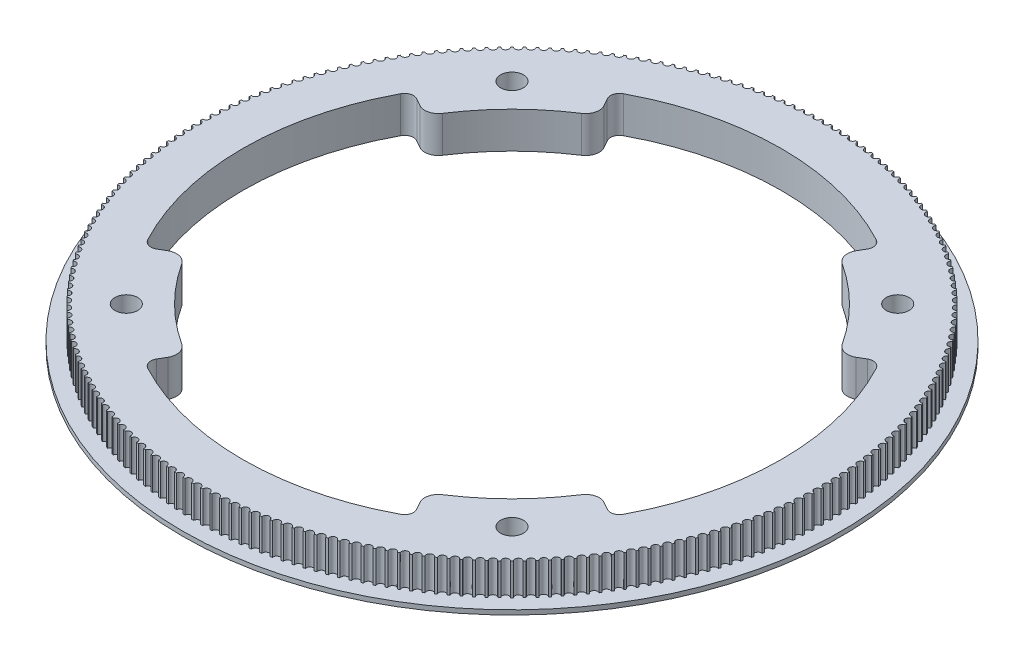
SolidWorks part; units mm, degrees
material "ABS"
ref_plane "Front Plane" through (0, 0, 0) normal (0, 0, 1) x (1, 0, 0)
ref_plane "Top Plane" through (0, 0, 0) normal (0, 1, 0) x (1, 0, 0)
ref_plane "Right Plane" through (0, 0, 0) normal (1, 0, 0) x (0, 0, -1)
sketch "Sketch1" plane through (0, 0, 0) normal (0, 1, 0) x (1, 0, 0)
  arc A0 (-0.76, 69.2508) -> (-1.2179, 69.2443) centre (0, 0) ccw
  arc A1 (-0.76, 69.2508) -> (0.76, 69.2508) centre (0, 69.255) ccw
  arc A2 (1.2179, 69.2443) -> (2.7372, 69.2009) centre (1.9776, 69.2268) ccw
  arc A3 (3.1947, 69.1813) -> (4.7122, 69.0945) centre (3.9537, 69.1421) ccw
  arc A4 (5.1689, 69.0618) -> (6.6833, 68.9318) centre (5.9265, 69.001) ccw
  arc A5 (7.139, 68.8861) -> (8.649, 68.7128) centre (7.8945, 68.8036) ccw
  arc A6 (9.1032, 68.6541) -> (10.6077, 68.4378) centre (9.856, 68.5501) ccw
  arc A7 (11.0599, 68.3662) -> (12.5577, 68.107) centre (11.8095, 68.2407) ccw
  arc A8 (13.0077, 68.0225) -> (14.4974, 67.7206) centre (13.7534, 67.8756) ccw
  arc A9 (14.9449, 67.6233) -> (16.4253, 67.279) centre (15.686, 67.4552) ccw
  arc A10 (16.8698, 67.1689) -> (18.3399, 66.7825) centre (17.6059, 66.9798) ccw
  arc A11 (18.781, 66.6598) -> (20.2394, 66.2316) centre (19.5114, 66.4497) ccw
  arc A12 (20.6769, 66.0963) -> (22.1225, 65.6266) centre (21.401, 65.8654) ccw
  arc A13 (22.5559, 65.4789) -> (23.9875, 64.9681) centre (23.2731, 65.2274) ccw
  arc A14 (24.4165, 64.8081) -> (25.8329, 64.2566) centre (25.1262, 64.5362) ccw
  arc A15 (26.2572, 64.0844) -> (27.6573, 63.4927) centre (26.9589, 63.7924) ccw
  arc A16 (28.0765, 63.3085) -> (29.4591, 62.6771) centre (28.7696, 62.9966) ccw
  arc A17 (29.8729, 62.4809) -> (31.2369, 61.8103) centre (30.5568, 62.1493) ccw
  arc A18 (31.6449, 61.6024) -> (32.9893, 60.8931) centre (32.319, 61.2514) ccw
  arc A19 (33.3912, 60.6736) -> (34.7147, 59.9262) centre (34.055, 60.3035) ccw
  arc A20 (35.1101, 59.6953) -> (36.4118, 58.9104) centre (35.7631, 59.3065) ccw
  arc A21 (36.8005, 58.6684) -> (38.0792, 57.8466) centre (37.4421, 58.261) ccw
  arc A22 (38.4608, 57.5936) -> (39.7155, 56.7356) centre (39.0905, 57.1681) ccw
  arc A23 (40.0898, 56.4718) -> (41.3195, 55.5784) centre (40.7071, 56.0285) ccw
  arc A24 (41.686, 55.304) -> (42.8897, 54.3758) centre (42.2904, 54.8432) ccw
  arc A25 (43.2483, 54.091) -> (44.425, 53.1289) centre (43.8393, 53.6132) ccw
  arc A26 (44.7753, 52.834) -> (45.924, 51.8386) centre (45.3524, 52.3394) ccw
  arc A27 (46.2658, 51.5338) -> (47.3856, 50.5061) centre (46.8285, 51.023) ccw
  arc A28 (47.7185, 50.1916) -> (48.8085, 49.1323) centre (48.2664, 49.665) ccw
  arc A29 (49.1323, 48.8085) -> (50.1916, 47.7185) centre (49.665, 48.2664) ccw
  arc A30 (50.5061, 47.3856) -> (51.5338, 46.2658) centre (51.023, 46.8285) ccw
  arc A31 (51.8386, 45.924) -> (52.834, 44.7753) centre (52.3394, 45.3524) ccw
  arc A32 (53.1289, 44.425) -> (54.091, 43.2483) centre (53.6132, 43.8393) ccw
  arc A33 (54.3758, 42.8897) -> (55.304, 41.686) centre (54.8432, 42.2904) ccw
  arc A34 (55.5784, 41.3195) -> (56.4718, 40.0898) centre (56.0285, 40.7071) ccw
  arc A35 (56.7356, 39.7155) -> (57.5936, 38.4608) centre (57.1681, 39.0905) ccw
  arc A36 (57.8466, 38.0792) -> (58.6684, 36.8005) centre (58.261, 37.4421) ccw
  arc A37 (58.9104, 36.4118) -> (59.6953, 35.1101) centre (59.3065, 35.7631) ccw
  arc A38 (59.9262, 34.7147) -> (60.6736, 33.3912) centre (60.3035, 34.055) ccw
  arc A39 (60.8931, 32.9893) -> (61.6024, 31.6449) centre (61.2514, 32.319) ccw
  arc A40 (61.8103, 31.2369) -> (62.4809, 29.8729) centre (62.1493, 30.5568) ccw
  arc A41 (62.6771, 29.4591) -> (63.3085, 28.0765) centre (62.9966, 28.7696) ccw
  arc A42 (63.4927, 27.6573) -> (64.0844, 26.2572) centre (63.7924, 26.9589) ccw
  arc A43 (64.2566, 25.8329) -> (64.8081, 24.4165) centre (64.5362, 25.1262) ccw
  arc A44 (64.9681, 23.9875) -> (65.4789, 22.5559) centre (65.2274, 23.2731) ccw
  arc A45 (65.6266, 22.1225) -> (66.0963, 20.6769) centre (65.8654, 21.401) ccw
  arc A46 (66.2316, 20.2394) -> (66.6598, 18.781) centre (66.4497, 19.5114) ccw
  arc A47 (66.7825, 18.3399) -> (67.1689, 16.8698) centre (66.9798, 17.6059) ccw
  arc A48 (67.279, 16.4253) -> (67.6233, 14.9449) centre (67.4552, 15.686) ccw
  arc A49 (67.7206, 14.4974) -> (68.0225, 13.0077) centre (67.8756, 13.7534) ccw
  arc A50 (68.107, 12.5577) -> (68.3662, 11.0599) centre (68.2407, 11.8095) ccw
  arc A51 (68.4378, 10.6077) -> (68.6541, 9.1032) centre (68.5501, 9.856) ccw
  arc A52 (68.7128, 8.649) -> (68.8861, 7.139) centre (68.8036, 7.8945) ccw
  arc A53 (68.9318, 6.6833) -> (69.0618, 5.1689) centre (69.001, 5.9265) ccw
  arc A54 (69.0945, 4.7122) -> (69.1813, 3.1947) centre (69.1421, 3.9537) ccw
  arc A55 (69.2009, 2.7372) -> (69.2443, 1.2179) centre (69.2268, 1.9776) ccw
  arc A56 (69.2508, 0.76) -> (69.2508, -0.76) centre (69.255, 0) ccw
  arc A57 (69.2443, -1.2179) -> (69.2009, -2.7372) centre (69.2268, -1.9776) ccw
  arc A58 (69.1813, -3.1947) -> (69.0945, -4.7122) centre (69.1421, -3.9537) ccw
  arc A59 (69.0618, -5.1689) -> (68.9318, -6.6833) centre (69.001, -5.9265) ccw
  arc A60 (68.8861, -7.139) -> (68.7128, -8.649) centre (68.8036, -7.8945) ccw
  arc A61 (68.6541, -9.1032) -> (68.4378, -10.6077) centre (68.5501, -9.856) ccw
  arc A62 (68.3662, -11.0599) -> (68.107, -12.5577) centre (68.2407, -11.8095) ccw
  arc A63 (68.0225, -13.0077) -> (67.7206, -14.4974) centre (67.8756, -13.7534) ccw
  arc A64 (67.6233, -14.9449) -> (67.279, -16.4253) centre (67.4552, -15.686) ccw
  arc A65 (67.1689, -16.8698) -> (66.7825, -18.3399) centre (66.9798, -17.6059) ccw
  arc A66 (66.6598, -18.781) -> (66.2316, -20.2394) centre (66.4497, -19.5114) ccw
  arc A67 (66.0963, -20.6769) -> (65.6266, -22.1225) centre (65.8654, -21.401) ccw
  arc A68 (65.4789, -22.5559) -> (64.9681, -23.9875) centre (65.2274, -23.2731) ccw
  arc A69 (64.8081, -24.4165) -> (64.2566, -25.8329) centre (64.5362, -25.1262) ccw
  arc A70 (64.0844, -26.2572) -> (63.4927, -27.6573) centre (63.7924, -26.9589) ccw
  arc A71 (63.3085, -28.0765) -> (62.6771, -29.4591) centre (62.9966, -28.7696) ccw
  arc A72 (62.4809, -29.8729) -> (61.8103, -31.2369) centre (62.1493, -30.5568) ccw
  arc A73 (61.6024, -31.6449) -> (60.8931, -32.9893) centre (61.2514, -32.319) ccw
  arc A74 (60.6736, -33.3912) -> (59.9262, -34.7147) centre (60.3035, -34.055) ccw
  arc A75 (59.6953, -35.1101) -> (58.9104, -36.4118) centre (59.3065, -35.7631) ccw
  arc A76 (58.6684, -36.8005) -> (57.8466, -38.0792) centre (58.261, -37.4421) ccw
  arc A77 (57.5936, -38.4608) -> (56.7356, -39.7155) centre (57.1681, -39.0905) ccw
  arc A78 (56.4718, -40.0898) -> (55.5784, -41.3195) centre (56.0285, -40.7071) ccw
  arc A79 (55.304, -41.686) -> (54.3758, -42.8897) centre (54.8432, -42.2904) ccw
  arc A80 (54.091, -43.2483) -> (53.1289, -44.425) centre (53.6132, -43.8393) ccw
  arc A81 (52.834, -44.7753) -> (51.8386, -45.924) centre (52.3394, -45.3524) ccw
  arc A82 (51.5338, -46.2658) -> (50.5061, -47.3856) centre (51.023, -46.8285) ccw
  arc A83 (50.1916, -47.7185) -> (49.1323, -48.8085) centre (49.665, -48.2664) ccw
  arc A84 (48.8085, -49.1323) -> (47.7185, -50.1916) centre (48.2664, -49.665) ccw
  arc A85 (47.3856, -50.5061) -> (46.2658, -51.5338) centre (46.8285, -51.023) ccw
  arc A86 (45.924, -51.8386) -> (44.7753, -52.834) centre (45.3524, -52.3394) ccw
  arc A87 (44.425, -53.1289) -> (43.2483, -54.091) centre (43.8393, -53.6132) ccw
  arc A88 (42.8897, -54.3758) -> (41.686, -55.304) centre (42.2904, -54.8432) ccw
  arc A89 (41.3195, -55.5784) -> (40.0898, -56.4718) centre (40.7071, -56.0285) ccw
  arc A90 (39.7155, -56.7356) -> (38.4608, -57.5936) centre (39.0905, -57.1681) ccw
  arc A91 (38.0792, -57.8466) -> (36.8005, -58.6684) centre (37.4421, -58.261) ccw
  arc A92 (36.4118, -58.9104) -> (35.1101, -59.6953) centre (35.7631, -59.3065) ccw
  arc A93 (34.7147, -59.9262) -> (33.3912, -60.6736) centre (34.055, -60.3035) ccw
  arc A94 (32.9893, -60.8931) -> (31.6449, -61.6024) centre (32.319, -61.2514) ccw
  arc A95 (31.2369, -61.8103) -> (29.8729, -62.4809) centre (30.5568, -62.1493) ccw
  arc A96 (29.4591, -62.6771) -> (28.0765, -63.3085) centre (28.7696, -62.9966) ccw
  arc A97 (27.6573, -63.4927) -> (26.2572, -64.0844) centre (26.9589, -63.7924) ccw
  arc A98 (25.8329, -64.2566) -> (24.4165, -64.8081) centre (25.1262, -64.5362) ccw
  arc A99 (23.9875, -64.9681) -> (22.5559, -65.4789) centre (23.2731, -65.2274) ccw
  arc A100 (22.1225, -65.6266) -> (20.6769, -66.0963) centre (21.401, -65.8654) ccw
  arc A101 (20.2394, -66.2316) -> (18.781, -66.6598) centre (19.5114, -66.4497) ccw
  arc A102 (18.3399, -66.7825) -> (16.8698, -67.1689) centre (17.6059, -66.9798) ccw
  arc A103 (16.4253, -67.279) -> (14.9449, -67.6233) centre (15.686, -67.4552) ccw
  arc A104 (14.4974, -67.7206) -> (13.0077, -68.0225) centre (13.7534, -67.8756) ccw
  arc A105 (12.5577, -68.107) -> (11.0599, -68.3662) centre (11.8095, -68.2407) ccw
  arc A106 (10.6077, -68.4378) -> (9.1032, -68.6541) centre (9.856, -68.5501) ccw
  arc A107 (8.649, -68.7128) -> (7.139, -68.8861) centre (7.8945, -68.8036) ccw
  arc A108 (6.6833, -68.9318) -> (5.1689, -69.0618) centre (5.9265, -69.001) ccw
  arc A109 (4.7122, -69.0945) -> (3.1947, -69.1813) centre (3.9537, -69.1421) ccw
  arc A110 (2.7372, -69.2009) -> (1.2179, -69.2443) centre (1.9776, -69.2268) ccw
  arc A111 (0.76, -69.2508) -> (-0.76, -69.2508) centre (0, -69.255) ccw
  arc A112 (-1.2179, -69.2443) -> (-2.7372, -69.2009) centre (-1.9776, -69.2268) ccw
  arc A113 (-3.1947, -69.1813) -> (-4.7122, -69.0945) centre (-3.9537, -69.1421) ccw
  arc A114 (-5.1689, -69.0618) -> (-6.6833, -68.9318) centre (-5.9265, -69.001) ccw
  arc A115 (-7.139, -68.8861) -> (-8.649, -68.7128) centre (-7.8945, -68.8036) ccw
  arc A116 (-9.1032, -68.6541) -> (-10.6077, -68.4378) centre (-9.856, -68.5501) ccw
  arc A117 (-11.0599, -68.3662) -> (-12.5577, -68.107) centre (-11.8095, -68.2407) ccw
  arc A118 (-13.0077, -68.0225) -> (-14.4974, -67.7206) centre (-13.7534, -67.8756) ccw
  arc A119 (-14.9449, -67.6233) -> (-16.4253, -67.279) centre (-15.686, -67.4552) ccw
  arc A120 (-16.8698, -67.1689) -> (-18.3399, -66.7825) centre (-17.6059, -66.9798) ccw
  arc A121 (-18.781, -66.6598) -> (-20.2394, -66.2316) centre (-19.5114, -66.4497) ccw
  arc A122 (-20.6769, -66.0963) -> (-22.1225, -65.6266) centre (-21.401, -65.8654) ccw
  arc A123 (-22.5559, -65.4789) -> (-23.9875, -64.9681) centre (-23.2731, -65.2274) ccw
  arc A124 (-24.4165, -64.8081) -> (-25.8329, -64.2566) centre (-25.1262, -64.5362) ccw
  arc A125 (-26.2572, -64.0844) -> (-27.6573, -63.4927) centre (-26.9589, -63.7924) ccw
  arc A126 (-28.0765, -63.3085) -> (-29.4591, -62.6771) centre (-28.7696, -62.9966) ccw
  arc A127 (-29.8729, -62.4809) -> (-31.2369, -61.8103) centre (-30.5568, -62.1493) ccw
  arc A128 (-31.6449, -61.6024) -> (-32.9893, -60.8931) centre (-32.319, -61.2514) ccw
  arc A129 (-33.3912, -60.6736) -> (-34.7147, -59.9262) centre (-34.055, -60.3035) ccw
  arc A130 (-35.1101, -59.6953) -> (-36.4118, -58.9104) centre (-35.7631, -59.3065) ccw
  arc A131 (-36.8005, -58.6684) -> (-38.0792, -57.8466) centre (-37.4421, -58.261) ccw
  arc A132 (-38.4608, -57.5936) -> (-39.7155, -56.7356) centre (-39.0905, -57.1681) ccw
  arc A133 (-40.0898, -56.4718) -> (-41.3195, -55.5784) centre (-40.7071, -56.0285) ccw
  arc A134 (-41.686, -55.304) -> (-42.8897, -54.3758) centre (-42.2904, -54.8432) ccw
  arc A135 (-43.2483, -54.091) -> (-44.425, -53.1289) centre (-43.8393, -53.6132) ccw
  arc A136 (-44.7753, -52.834) -> (-45.924, -51.8386) centre (-45.3524, -52.3394) ccw
  arc A137 (-46.2658, -51.5338) -> (-47.3856, -50.5061) centre (-46.8285, -51.023) ccw
  arc A138 (-47.7185, -50.1916) -> (-48.8085, -49.1323) centre (-48.2664, -49.665) ccw
  arc A139 (-49.1323, -48.8085) -> (-50.1916, -47.7185) centre (-49.665, -48.2664) ccw
  arc A140 (-50.5061, -47.3856) -> (-51.5338, -46.2658) centre (-51.023, -46.8285) ccw
  arc A141 (-51.8386, -45.924) -> (-52.834, -44.7753) centre (-52.3394, -45.3524) ccw
  arc A142 (-53.1289, -44.425) -> (-54.091, -43.2483) centre (-53.6132, -43.8393) ccw
  arc A143 (-54.3758, -42.8897) -> (-55.304, -41.686) centre (-54.8432, -42.2904) ccw
  arc A144 (-55.5784, -41.3195) -> (-56.4718, -40.0898) centre (-56.0285, -40.7071) ccw
  arc A145 (-56.7356, -39.7155) -> (-57.5936, -38.4608) centre (-57.1681, -39.0905) ccw
  arc A146 (-57.8466, -38.0792) -> (-58.6684, -36.8005) centre (-58.261, -37.4421) ccw
  arc A147 (-58.9104, -36.4118) -> (-59.6953, -35.1101) centre (-59.3065, -35.7631) ccw
  arc A148 (-59.9262, -34.7147) -> (-60.6736, -33.3912) centre (-60.3035, -34.055) ccw
  arc A149 (-60.8931, -32.9893) -> (-61.6024, -31.6449) centre (-61.2514, -32.319) ccw
  arc A150 (-61.8103, -31.2369) -> (-62.4809, -29.8729) centre (-62.1493, -30.5568) ccw
  arc A151 (-62.6771, -29.4591) -> (-63.3085, -28.0765) centre (-62.9966, -28.7696) ccw
  arc A152 (-63.4927, -27.6573) -> (-64.0844, -26.2572) centre (-63.7924, -26.9589) ccw
  arc A153 (-64.2566, -25.8329) -> (-64.8081, -24.4165) centre (-64.5362, -25.1262) ccw
  arc A154 (-64.9681, -23.9875) -> (-65.4789, -22.5559) centre (-65.2274, -23.2731) ccw
  arc A155 (-65.6266, -22.1225) -> (-66.0963, -20.6769) centre (-65.8654, -21.401) ccw
  arc A156 (-66.2316, -20.2394) -> (-66.6598, -18.781) centre (-66.4497, -19.5114) ccw
  arc A157 (-66.7825, -18.3399) -> (-67.1689, -16.8698) centre (-66.9798, -17.6059) ccw
  arc A158 (-67.279, -16.4253) -> (-67.6233, -14.9449) centre (-67.4552, -15.686) ccw
  arc A159 (-67.7206, -14.4974) -> (-68.0225, -13.0077) centre (-67.8756, -13.7534) ccw
  arc A160 (-68.107, -12.5577) -> (-68.3662, -11.0599) centre (-68.2407, -11.8095) ccw
  arc A161 (-68.4378, -10.6077) -> (-68.6541, -9.1032) centre (-68.5501, -9.856) ccw
  arc A162 (-68.7128, -8.649) -> (-68.8861, -7.139) centre (-68.8036, -7.8945) ccw
  arc A163 (-68.9318, -6.6833) -> (-69.0618, -5.1689) centre (-69.001, -5.9265) ccw
  arc A164 (-69.0945, -4.7122) -> (-69.1813, -3.1947) centre (-69.1421, -3.9537) ccw
  arc A165 (-69.2009, -2.7372) -> (-69.2443, -1.2179) centre (-69.2268, -1.9776) ccw
  arc A166 (-69.2508, -0.76) -> (-69.2508, 0.76) centre (-69.255, 0) ccw
  arc A167 (-69.2443, 1.2179) -> (-69.2009, 2.7372) centre (-69.2268, 1.9776) ccw
  arc A168 (-69.1813, 3.1947) -> (-69.0945, 4.7122) centre (-69.1421, 3.9537) ccw
  arc A169 (-69.0618, 5.1689) -> (-68.9318, 6.6833) centre (-69.001, 5.9265) ccw
  arc A170 (-68.8861, 7.139) -> (-68.7128, 8.649) centre (-68.8036, 7.8945) ccw
  arc A171 (-68.6541, 9.1032) -> (-68.4378, 10.6077) centre (-68.5501, 9.856) ccw
  arc A172 (-68.3662, 11.0599) -> (-68.107, 12.5577) centre (-68.2407, 11.8095) ccw
  arc A173 (-68.0225, 13.0077) -> (-67.7206, 14.4974) centre (-67.8756, 13.7534) ccw
  arc A174 (-67.6233, 14.9449) -> (-67.279, 16.4253) centre (-67.4552, 15.686) ccw
  arc A175 (-67.1689, 16.8698) -> (-66.7825, 18.3399) centre (-66.9798, 17.6059) ccw
  arc A176 (-66.6598, 18.781) -> (-66.2316, 20.2394) centre (-66.4497, 19.5114) ccw
  arc A177 (-66.0963, 20.6769) -> (-65.6266, 22.1225) centre (-65.8654, 21.401) ccw
  arc A178 (-65.4789, 22.5559) -> (-64.9681, 23.9875) centre (-65.2274, 23.2731) ccw
  arc A179 (-64.8081, 24.4165) -> (-64.2566, 25.8329) centre (-64.5362, 25.1262) ccw
  arc A180 (-64.0844, 26.2572) -> (-63.4927, 27.6573) centre (-63.7924, 26.9589) ccw
  arc A181 (-63.3085, 28.0765) -> (-62.6771, 29.4591) centre (-62.9966, 28.7696) ccw
  arc A182 (-62.4809, 29.8729) -> (-61.8103, 31.2369) centre (-62.1493, 30.5568) ccw
  arc A183 (-61.6024, 31.6449) -> (-60.8931, 32.9893) centre (-61.2514, 32.319) ccw
  arc A184 (-60.6736, 33.3912) -> (-59.9262, 34.7147) centre (-60.3035, 34.055) ccw
  arc A185 (-59.6953, 35.1101) -> (-58.9104, 36.4118) centre (-59.3065, 35.7631) ccw
  arc A186 (-58.6684, 36.8005) -> (-57.8466, 38.0792) centre (-58.261, 37.4421) ccw
  arc A187 (-57.5936, 38.4608) -> (-56.7356, 39.7155) centre (-57.1681, 39.0905) ccw
  arc A188 (-56.4718, 40.0898) -> (-55.5784, 41.3195) centre (-56.0285, 40.7071) ccw
  arc A189 (-55.304, 41.686) -> (-54.3758, 42.8897) centre (-54.8432, 42.2904) ccw
  arc A190 (-54.091, 43.2483) -> (-53.1289, 44.425) centre (-53.6132, 43.8393) ccw
  arc A191 (-52.834, 44.7753) -> (-51.8386, 45.924) centre (-52.3394, 45.3524) ccw
  arc A192 (-51.5338, 46.2658) -> (-50.5061, 47.3856) centre (-51.023, 46.8285) ccw
  arc A193 (-50.1916, 47.7185) -> (-49.1323, 48.8085) centre (-49.665, 48.2664) ccw
  arc A194 (-48.8085, 49.1323) -> (-47.7185, 50.1916) centre (-48.2664, 49.665) ccw
  arc A195 (-47.3856, 50.5061) -> (-46.2658, 51.5338) centre (-46.8285, 51.023) ccw
  arc A196 (-45.924, 51.8386) -> (-44.7753, 52.834) centre (-45.3524, 52.3394) ccw
  arc A197 (-44.425, 53.1289) -> (-43.2483, 54.091) centre (-43.8393, 53.6132) ccw
  arc A198 (-42.8897, 54.3758) -> (-41.686, 55.304) centre (-42.2904, 54.8432) ccw
  arc A199 (-41.3195, 55.5784) -> (-40.0898, 56.4718) centre (-40.7071, 56.0285) ccw
  arc A200 (-39.7155, 56.7356) -> (-38.4608, 57.5936) centre (-39.0905, 57.1681) ccw
  arc A201 (-38.0792, 57.8466) -> (-36.8005, 58.6684) centre (-37.4421, 58.261) ccw
  arc A202 (-36.4118, 58.9104) -> (-35.1101, 59.6953) centre (-35.7631, 59.3065) ccw
  arc A203 (-34.7147, 59.9262) -> (-33.3912, 60.6736) centre (-34.055, 60.3035) ccw
  arc A204 (-32.9893, 60.8931) -> (-31.6449, 61.6024) centre (-32.319, 61.2514) ccw
  arc A205 (-31.2369, 61.8103) -> (-29.8729, 62.4809) centre (-30.5568, 62.1493) ccw
  arc A206 (-29.4591, 62.6771) -> (-28.0765, 63.3085) centre (-28.7696, 62.9966) ccw
  arc A207 (-27.6573, 63.4927) -> (-26.2572, 64.0844) centre (-26.9589, 63.7924) ccw
  arc A208 (-25.8329, 64.2566) -> (-24.4165, 64.8081) centre (-25.1262, 64.5362) ccw
  arc A209 (-23.9875, 64.9681) -> (-22.5559, 65.4789) centre (-23.2731, 65.2274) ccw
  arc A210 (-22.1225, 65.6266) -> (-20.6769, 66.0963) centre (-21.401, 65.8654) ccw
  arc A211 (-20.2394, 66.2316) -> (-18.781, 66.6598) centre (-19.5114, 66.4497) ccw
  arc A212 (-18.3399, 66.7825) -> (-16.8698, 67.1689) centre (-17.6059, 66.9798) ccw
  arc A213 (-16.4253, 67.279) -> (-14.9449, 67.6233) centre (-15.686, 67.4552) ccw
  arc A214 (-14.4974, 67.7206) -> (-13.0077, 68.0225) centre (-13.7534, 67.8756) ccw
  arc A215 (-12.5577, 68.107) -> (-11.0599, 68.3662) centre (-11.8095, 68.2407) ccw
  arc A216 (-10.6077, 68.4378) -> (-9.1032, 68.6541) centre (-9.856, 68.5501) ccw
  arc A217 (-8.649, 68.7128) -> (-7.139, 68.8861) centre (-7.8945, 68.8036) ccw
  arc A218 (-6.6833, 68.9318) -> (-5.1689, 69.0618) centre (-5.9265, 69.001) ccw
  arc A219 (-4.7122, 69.0945) -> (-3.1947, 69.1813) centre (-3.9537, 69.1421) ccw
  arc A220 (-2.7372, 69.2009) -> (-1.2179, 69.2443) centre (-1.9776, 69.2268) ccw
  arc A221 (1.2179, 69.2443) -> (0.76, 69.2508) centre (0, 0) ccw
  arc A222 (3.1947, 69.1813) -> (2.7372, 69.2009) centre (0, 0) ccw
  arc A223 (5.1689, 69.0618) -> (4.7122, 69.0945) centre (0, 0) ccw
  arc A224 (7.139, 68.8861) -> (6.6833, 68.9318) centre (0, 0) ccw
  arc A225 (9.1032, 68.6541) -> (8.649, 68.7128) centre (0, 0) ccw
  arc A226 (11.0599, 68.3662) -> (10.6077, 68.4378) centre (0, 0) ccw
  arc A227 (13.0077, 68.0225) -> (12.5577, 68.107) centre (0, 0) ccw
  arc A228 (14.9449, 67.6233) -> (14.4974, 67.7206) centre (0, 0) ccw
  arc A229 (16.8698, 67.1689) -> (16.4253, 67.279) centre (0, 0) ccw
  arc A230 (18.781, 66.6598) -> (18.3399, 66.7825) centre (0, 0) ccw
  arc A231 (20.6769, 66.0963) -> (20.2394, 66.2316) centre (0, 0) ccw
  arc A232 (22.5559, 65.4789) -> (22.1225, 65.6266) centre (0, 0) ccw
  arc A233 (24.4165, 64.8081) -> (23.9875, 64.9681) centre (0, 0) ccw
  arc A234 (26.2572, 64.0844) -> (25.8329, 64.2566) centre (0, 0) ccw
  arc A235 (28.0765, 63.3085) -> (27.6573, 63.4927) centre (0, 0) ccw
  arc A236 (29.8729, 62.4809) -> (29.4591, 62.6771) centre (0, 0) ccw
  arc A237 (31.6449, 61.6024) -> (31.2369, 61.8103) centre (0, 0) ccw
  arc A238 (33.3912, 60.6736) -> (32.9893, 60.8931) centre (0, 0) ccw
  arc A239 (35.1101, 59.6953) -> (34.7147, 59.9262) centre (0, 0) ccw
  arc A240 (36.8005, 58.6684) -> (36.4118, 58.9104) centre (0, 0) ccw
  arc A241 (38.4608, 57.5936) -> (38.0792, 57.8466) centre (0, 0) ccw
  arc A242 (40.0898, 56.4718) -> (39.7155, 56.7356) centre (0, 0) ccw
  arc A243 (41.686, 55.304) -> (41.3195, 55.5784) centre (0, 0) ccw
  arc A244 (43.2483, 54.091) -> (42.8897, 54.3758) centre (0, 0) ccw
  arc A245 (44.7753, 52.834) -> (44.425, 53.1289) centre (0, 0) ccw
  arc A246 (46.2658, 51.5338) -> (45.924, 51.8386) centre (0, 0) ccw
  arc A247 (47.7185, 50.1916) -> (47.3856, 50.5061) centre (0, 0) ccw
  arc A248 (49.1323, 48.8085) -> (48.8085, 49.1323) centre (0, 0) ccw
  arc A249 (50.5061, 47.3856) -> (50.1916, 47.7185) centre (0, 0) ccw
  arc A250 (51.8386, 45.924) -> (51.5338, 46.2658) centre (0, 0) ccw
  arc A251 (53.1289, 44.425) -> (52.834, 44.7753) centre (0, 0) ccw
  arc A252 (54.3758, 42.8897) -> (54.091, 43.2483) centre (0, 0) ccw
  arc A253 (55.5784, 41.3195) -> (55.304, 41.686) centre (0, 0) ccw
  arc A254 (56.7356, 39.7155) -> (56.4718, 40.0898) centre (0, 0) ccw
  arc A255 (57.8466, 38.0792) -> (57.5936, 38.4608) centre (0, 0) ccw
  arc A256 (58.9104, 36.4118) -> (58.6684, 36.8005) centre (0, 0) ccw
  arc A257 (59.9262, 34.7147) -> (59.6953, 35.1101) centre (0, 0) ccw
  arc A258 (60.8931, 32.9893) -> (60.6736, 33.3912) centre (0, 0) ccw
  arc A259 (61.8103, 31.2369) -> (61.6024, 31.6449) centre (0, 0) ccw
  arc A260 (62.6771, 29.4591) -> (62.4809, 29.8729) centre (0, 0) ccw
  arc A261 (63.4927, 27.6573) -> (63.3085, 28.0765) centre (0, 0) ccw
  arc A262 (64.2566, 25.8329) -> (64.0844, 26.2572) centre (0, 0) ccw
  arc A263 (64.9681, 23.9875) -> (64.8081, 24.4165) centre (0, 0) ccw
  arc A264 (65.6266, 22.1225) -> (65.4789, 22.5559) centre (0, 0) ccw
  arc A265 (66.2316, 20.2394) -> (66.0963, 20.6769) centre (0, 0) ccw
  arc A266 (66.7825, 18.3399) -> (66.6598, 18.781) centre (0, 0) ccw
  arc A267 (67.279, 16.4253) -> (67.1689, 16.8698) centre (0, 0) ccw
  arc A268 (67.7206, 14.4974) -> (67.6233, 14.9449) centre (0, 0) ccw
  arc A269 (68.107, 12.5577) -> (68.0225, 13.0077) centre (0, 0) ccw
  arc A270 (68.4378, 10.6077) -> (68.3662, 11.0599) centre (0, 0) ccw
  arc A271 (68.7128, 8.649) -> (68.6541, 9.1032) centre (0, 0) ccw
  arc A272 (68.9318, 6.6833) -> (68.8861, 7.139) centre (0, 0) ccw
  arc A273 (69.0945, 4.7122) -> (69.0618, 5.1689) centre (0, 0) ccw
  arc A274 (69.2009, 2.7372) -> (69.1813, 3.1947) centre (0, 0) ccw
  arc A275 (69.2508, 0.76) -> (69.2443, 1.2179) centre (0, 0) ccw
  arc A276 (69.2443, -1.2179) -> (69.2508, -0.76) centre (0, 0) ccw
  arc A277 (69.1813, -3.1947) -> (69.2009, -2.7372) centre (0, 0) ccw
  arc A278 (69.0618, -5.1689) -> (69.0945, -4.7122) centre (0, 0) ccw
  arc A279 (68.8861, -7.139) -> (68.9318, -6.6833) centre (0, 0) ccw
  arc A280 (68.6541, -9.1032) -> (68.7128, -8.649) centre (0, 0) ccw
  arc A281 (68.3662, -11.0599) -> (68.4378, -10.6077) centre (0, 0) ccw
  arc A282 (68.0225, -13.0077) -> (68.107, -12.5577) centre (0, 0) ccw
  arc A283 (67.6233, -14.9449) -> (67.7206, -14.4974) centre (0, 0) ccw
  arc A284 (67.1689, -16.8698) -> (67.279, -16.4253) centre (0, 0) ccw
  arc A285 (66.6598, -18.781) -> (66.7825, -18.3399) centre (0, 0) ccw
  arc A286 (66.0963, -20.6769) -> (66.2316, -20.2394) centre (0, 0) ccw
  arc A287 (65.4789, -22.5559) -> (65.6266, -22.1225) centre (0, 0) ccw
  arc A288 (64.8081, -24.4165) -> (64.9681, -23.9875) centre (0, 0) ccw
  arc A289 (64.0844, -26.2572) -> (64.2566, -25.8329) centre (0, 0) ccw
  arc A290 (63.3085, -28.0765) -> (63.4927, -27.6573) centre (0, 0) ccw
  arc A291 (62.4809, -29.8729) -> (62.6771, -29.4591) centre (0, 0) ccw
  arc A292 (61.6024, -31.6449) -> (61.8103, -31.2369) centre (0, 0) ccw
  arc A293 (60.6736, -33.3912) -> (60.8931, -32.9893) centre (0, 0) ccw
  arc A294 (59.6953, -35.1101) -> (59.9262, -34.7147) centre (0, 0) ccw
  arc A295 (58.6684, -36.8005) -> (58.9104, -36.4118) centre (0, 0) ccw
  arc A296 (57.5936, -38.4608) -> (57.8466, -38.0792) centre (0, 0) ccw
  arc A297 (56.4718, -40.0898) -> (56.7356, -39.7155) centre (0, 0) ccw
  arc A298 (55.304, -41.686) -> (55.5784, -41.3195) centre (0, 0) ccw
  arc A299 (54.091, -43.2483) -> (54.3758, -42.8897) centre (0, 0) ccw
  arc A300 (52.834, -44.7753) -> (53.1289, -44.425) centre (0, 0) ccw
  arc A301 (51.5338, -46.2658) -> (51.8386, -45.924) centre (0, 0) ccw
  arc A302 (50.1916, -47.7185) -> (50.5061, -47.3856) centre (0, 0) ccw
  arc A303 (48.8085, -49.1323) -> (49.1323, -48.8085) centre (0, 0) ccw
  arc A304 (47.3856, -50.5061) -> (47.7185, -50.1916) centre (0, 0) ccw
  arc A305 (45.924, -51.8386) -> (46.2658, -51.5338) centre (0, 0) ccw
  arc A306 (44.425, -53.1289) -> (44.7753, -52.834) centre (0, 0) ccw
  arc A307 (42.8897, -54.3758) -> (43.2483, -54.091) centre (0, 0) ccw
  arc A308 (41.3195, -55.5784) -> (41.686, -55.304) centre (0, 0) ccw
  arc A309 (39.7155, -56.7356) -> (40.0898, -56.4718) centre (0, 0) ccw
  arc A310 (38.0792, -57.8466) -> (38.4608, -57.5936) centre (0, 0) ccw
  arc A311 (36.4118, -58.9104) -> (36.8005, -58.6684) centre (0, 0) ccw
  arc A312 (34.7147, -59.9262) -> (35.1101, -59.6953) centre (0, 0) ccw
  arc A313 (32.9893, -60.8931) -> (33.3912, -60.6736) centre (0, 0) ccw
  arc A314 (31.2369, -61.8103) -> (31.6449, -61.6024) centre (0, 0) ccw
  arc A315 (29.4591, -62.6771) -> (29.8729, -62.4809) centre (0, 0) ccw
  arc A316 (27.6573, -63.4927) -> (28.0765, -63.3085) centre (0, 0) ccw
  arc A317 (23.9875, -64.9681) -> (24.4165, -64.8081) centre (0, 0) ccw
  arc A318 (25.8329, -64.2566) -> (26.2572, -64.0844) centre (0, 0) ccw
  arc A319 (22.1225, -65.6266) -> (22.5559, -65.4789) centre (0, 0) ccw
  arc A320 (20.2394, -66.2316) -> (20.6769, -66.0963) centre (0, 0) ccw
  arc A321 (18.3399, -66.7825) -> (18.781, -66.6598) centre (0, 0) ccw
  arc A322 (16.4253, -67.279) -> (16.8698, -67.1689) centre (0, 0) ccw
  arc A323 (14.4974, -67.7206) -> (14.9449, -67.6233) centre (0, 0) ccw
  arc A324 (12.5577, -68.107) -> (13.0077, -68.0225) centre (0, 0) ccw
  arc A325 (10.6077, -68.4378) -> (11.0599, -68.3662) centre (0, 0) ccw
  arc A326 (8.649, -68.7128) -> (9.1032, -68.6541) centre (0, 0) ccw
  arc A327 (6.6833, -68.9318) -> (7.139, -68.8861) centre (0, 0) ccw
  arc A328 (4.7122, -69.0945) -> (5.1689, -69.0618) centre (0, 0) ccw
  arc A329 (2.7372, -69.2009) -> (3.1947, -69.1813) centre (0, 0) ccw
  arc A330 (0.76, -69.2508) -> (1.2179, -69.2443) centre (0, 0) ccw
  arc A331 (-1.2179, -69.2443) -> (-0.76, -69.2508) centre (0, 0) ccw
  arc A332 (-3.1947, -69.1813) -> (-2.7372, -69.2009) centre (0, 0) ccw
  arc A333 (-5.1689, -69.0618) -> (-4.7122, -69.0945) centre (0, 0) ccw
  arc A334 (-7.139, -68.8861) -> (-6.6833, -68.9318) centre (0, 0) ccw
  arc A335 (-9.1032, -68.6541) -> (-8.649, -68.7128) centre (0, 0) ccw
  arc A336 (-11.0599, -68.3662) -> (-10.6077, -68.4378) centre (0, 0) ccw
  arc A337 (-13.0077, -68.0225) -> (-12.5577, -68.107) centre (0, 0) ccw
  arc A338 (-14.9449, -67.6233) -> (-14.4974, -67.7206) centre (0, 0) ccw
  arc A339 (-16.8698, -67.1689) -> (-16.4253, -67.279) centre (0, 0) ccw
  arc A340 (-18.781, -66.6598) -> (-18.3399, -66.7825) centre (0, 0) ccw
  arc A341 (-20.6769, -66.0963) -> (-20.2394, -66.2316) centre (0, 0) ccw
  arc A342 (-22.5559, -65.4789) -> (-22.1225, -65.6266) centre (0, 0) ccw
  arc A343 (-24.4165, -64.8081) -> (-23.9875, -64.9681) centre (0, 0) ccw
  arc A344 (-26.2572, -64.0844) -> (-25.8329, -64.2566) centre (0, 0) ccw
  arc A345 (-28.0765, -63.3085) -> (-27.6573, -63.4927) centre (0, 0) ccw
  arc A346 (-29.8729, -62.4809) -> (-29.4591, -62.6771) centre (0, 0) ccw
  arc A347 (-31.6449, -61.6024) -> (-31.2369, -61.8103) centre (0, 0) ccw
  arc A348 (-33.3912, -60.6736) -> (-32.9893, -60.8931) centre (0, 0) ccw
  arc A349 (-35.1101, -59.6953) -> (-34.7147, -59.9262) centre (0, 0) ccw
  arc A350 (-36.8005, -58.6684) -> (-36.4118, -58.9104) centre (0, 0) ccw
  arc A351 (-38.4608, -57.5936) -> (-38.0792, -57.8466) centre (0, 0) ccw
  arc A352 (-40.0898, -56.4718) -> (-39.7155, -56.7356) centre (0, 0) ccw
  arc A353 (-41.686, -55.304) -> (-41.3195, -55.5784) centre (0, 0) ccw
  arc A354 (-43.2483, -54.091) -> (-42.8897, -54.3758) centre (0, 0) ccw
  arc A355 (-44.7753, -52.834) -> (-44.425, -53.1289) centre (0, 0) ccw
  arc A356 (-46.2658, -51.5338) -> (-45.924, -51.8386) centre (0, 0) ccw
  arc A357 (-47.7185, -50.1916) -> (-47.3856, -50.5061) centre (0, 0) ccw
  arc A358 (-49.1323, -48.8085) -> (-48.8085, -49.1323) centre (0, 0) ccw
  arc A359 (-50.5061, -47.3856) -> (-50.1916, -47.7185) centre (0, 0) ccw
  arc A360 (-51.8386, -45.924) -> (-51.5338, -46.2658) centre (0, 0) ccw
  arc A361 (-53.1289, -44.425) -> (-52.834, -44.7753) centre (0, 0) ccw
  arc A362 (-54.3758, -42.8897) -> (-54.091, -43.2483) centre (0, 0) ccw
  arc A363 (-55.5784, -41.3195) -> (-55.304, -41.686) centre (0, 0) ccw
  arc A364 (-56.7356, -39.7155) -> (-56.4718, -40.0898) centre (0, 0) ccw
  arc A365 (-57.8466, -38.0792) -> (-57.5936, -38.4608) centre (0, 0) ccw
  arc A366 (-58.9104, -36.4118) -> (-58.6684, -36.8005) centre (0, 0) ccw
  arc A367 (-59.9262, -34.7147) -> (-59.6953, -35.1101) centre (0, 0) ccw
  arc A368 (-60.8931, -32.9893) -> (-60.6736, -33.3912) centre (0, 0) ccw
  arc A369 (-61.8103, -31.2369) -> (-61.6024, -31.6449) centre (0, 0) ccw
  arc A370 (-62.6771, -29.4591) -> (-62.4809, -29.8729) centre (0, 0) ccw
  arc A371 (-63.4927, -27.6573) -> (-63.3085, -28.0765) centre (0, 0) ccw
  arc A372 (-64.2566, -25.8329) -> (-64.0844, -26.2572) centre (0, 0) ccw
  arc A373 (-64.9681, -23.9875) -> (-64.8081, -24.4165) centre (0, 0) ccw
  arc A374 (-65.6266, -22.1225) -> (-65.4789, -22.5559) centre (0, 0) ccw
  arc A375 (-66.2316, -20.2394) -> (-66.0963, -20.6769) centre (0, 0) ccw
  arc A376 (-66.7825, -18.3399) -> (-66.6598, -18.781) centre (0, 0) ccw
  arc A377 (-67.279, -16.4253) -> (-67.1689, -16.8698) centre (0, 0) ccw
  arc A378 (-67.7206, -14.4974) -> (-67.6233, -14.9449) centre (0, 0) ccw
  arc A379 (-68.107, -12.5577) -> (-68.0225, -13.0077) centre (0, 0) ccw
  arc A380 (-68.4378, -10.6077) -> (-68.3662, -11.0599) centre (0, 0) ccw
  arc A381 (-68.7128, -8.649) -> (-68.6541, -9.1032) centre (0, 0) ccw
  arc A382 (-68.9318, -6.6833) -> (-68.8861, -7.139) centre (0, 0) ccw
  arc A383 (-69.0945, -4.7122) -> (-69.0618, -5.1689) centre (0, 0) ccw
  arc A384 (-69.2009, -2.7372) -> (-69.1813, -3.1947) centre (0, 0) ccw
  arc A385 (-69.2508, -0.76) -> (-69.2443, -1.2179) centre (0, 0) ccw
  arc A386 (-69.2443, 1.2179) -> (-69.2508, 0.76) centre (0, 0) ccw
  arc A387 (-69.1813, 3.1947) -> (-69.2009, 2.7372) centre (0, 0) ccw
  arc A388 (-69.0618, 5.1689) -> (-69.0945, 4.7122) centre (0, 0) ccw
  arc A389 (-68.8861, 7.139) -> (-68.9318, 6.6833) centre (0, 0) ccw
  arc A390 (-68.6541, 9.1032) -> (-68.7128, 8.649) centre (0, 0) ccw
  arc A391 (-68.3662, 11.0599) -> (-68.4378, 10.6077) centre (0, 0) ccw
  arc A392 (-68.0225, 13.0077) -> (-68.107, 12.5577) centre (0, 0) ccw
  arc A393 (-67.6233, 14.9449) -> (-67.7206, 14.4974) centre (0, 0) ccw
  arc A394 (-67.1689, 16.8698) -> (-67.279, 16.4253) centre (0, 0) ccw
  arc A395 (-66.6598, 18.781) -> (-66.7825, 18.3399) centre (0, 0) ccw
  arc A396 (-66.0963, 20.6769) -> (-66.2316, 20.2394) centre (0, 0) ccw
  arc A397 (-65.4789, 22.5559) -> (-65.6266, 22.1225) centre (0, 0) ccw
  arc A398 (-64.8081, 24.4165) -> (-64.9681, 23.9875) centre (0, 0) ccw
  arc A399 (-64.0844, 26.2572) -> (-64.2566, 25.8329) centre (0, 0) ccw
  arc A400 (-63.3085, 28.0765) -> (-63.4927, 27.6573) centre (0, 0) ccw
  arc A401 (-62.4809, 29.8729) -> (-62.6771, 29.4591) centre (0, 0) ccw
  arc A402 (-61.6024, 31.6449) -> (-61.8103, 31.2369) centre (0, 0) ccw
  arc A403 (-60.6736, 33.3912) -> (-60.8931, 32.9893) centre (0, 0) ccw
  arc A404 (-59.6953, 35.1101) -> (-59.9262, 34.7147) centre (0, 0) ccw
  arc A405 (-58.6684, 36.8005) -> (-58.9104, 36.4118) centre (0, 0) ccw
  arc A406 (-57.5936, 38.4608) -> (-57.8466, 38.0792) centre (0, 0) ccw
  arc A407 (-56.4718, 40.0898) -> (-56.7356, 39.7155) centre (0, 0) ccw
  arc A408 (-55.304, 41.686) -> (-55.5784, 41.3195) centre (0, 0) ccw
  arc A409 (-54.091, 43.2483) -> (-54.3758, 42.8897) centre (0, 0) ccw
  arc A410 (-52.834, 44.7753) -> (-53.1289, 44.425) centre (0, 0) ccw
  arc A411 (-51.5338, 46.2658) -> (-51.8386, 45.924) centre (0, 0) ccw
  arc A412 (-50.1916, 47.7185) -> (-50.5061, 47.3856) centre (0, 0) ccw
  arc A413 (-48.8085, 49.1323) -> (-49.1323, 48.8085) centre (0, 0) ccw
  arc A414 (-47.3856, 50.5061) -> (-47.7185, 50.1916) centre (0, 0) ccw
  arc A415 (-45.924, 51.8386) -> (-46.2658, 51.5338) centre (0, 0) ccw
  arc A416 (-42.8897, 54.3758) -> (-43.2483, 54.091) centre (0, 0) ccw
  arc A417 (-44.425, 53.1289) -> (-44.7753, 52.834) centre (0, 0) ccw
  arc A418 (-41.3195, 55.5784) -> (-41.686, 55.304) centre (0, 0) ccw
  arc A419 (-39.7155, 56.7356) -> (-40.0898, 56.4718) centre (0, 0) ccw
  arc A420 (-38.0792, 57.8466) -> (-38.4608, 57.5936) centre (0, 0) ccw
  arc A421 (-36.4118, 58.9104) -> (-36.8005, 58.6684) centre (0, 0) ccw
  arc A422 (-34.7147, 59.9262) -> (-35.1101, 59.6953) centre (0, 0) ccw
  arc A423 (-32.9893, 60.8931) -> (-33.3912, 60.6736) centre (0, 0) ccw
  arc A424 (-31.2369, 61.8103) -> (-31.6449, 61.6024) centre (0, 0) ccw
  arc A425 (-29.4591, 62.6771) -> (-29.8729, 62.4809) centre (0, 0) ccw
  arc A426 (-27.6573, 63.4927) -> (-28.0765, 63.3085) centre (0, 0) ccw
  arc A427 (-25.8329, 64.2566) -> (-26.2572, 64.0844) centre (0, 0) ccw
  arc A428 (-23.9875, 64.9681) -> (-24.4165, 64.8081) centre (0, 0) ccw
  arc A429 (-22.1225, 65.6266) -> (-22.5559, 65.4789) centre (0, 0) ccw
  arc A430 (-20.2394, 66.2316) -> (-20.6769, 66.0963) centre (0, 0) ccw
  arc A431 (-18.3399, 66.7825) -> (-18.781, 66.6598) centre (0, 0) ccw
  arc A432 (-16.4253, 67.279) -> (-16.8698, 67.1689) centre (0, 0) ccw
  arc A433 (-14.4974, 67.7206) -> (-14.9449, 67.6233) centre (0, 0) ccw
  arc A434 (-12.5577, 68.107) -> (-13.0077, 68.0225) centre (0, 0) ccw
  arc A435 (-8.649, 68.7128) -> (-9.1032, 68.6541) centre (0, 0) ccw
  arc A436 (-10.6077, 68.4378) -> (-11.0599, 68.3662) centre (0, 0) ccw
  arc A437 (-6.6833, 68.9318) -> (-7.139, 68.8861) centre (0, 0) ccw
  arc A438 (-4.7122, 69.0945) -> (-5.1689, 69.0618) centre (0, 0) ccw
  arc A439 (-2.7372, 69.2009) -> (-3.1947, 69.1813) centre (0, 0) ccw
  point P665 (0, 0)
  dimension "D1" = 138.51
  dimension "D2" = 1.52
  dimension "D3" = 220
extrude "Boss-Extrude1" add sketch "Sketch1" along normal blind 7
sketch "Sketch3" plane through (0, 0, 0) normal (0, -1, 0) x (1, 0, 0)
  circle A0 centre (0, 0) radius 72.5
extrude "Boss-Extrude3" add sketch "Sketch3" along normal blind 1
sketch "Sketch6" plane through (0, 7, 0) normal (0, 1, 0) x (1, 0, 0)
  line L0 (0, 0) -> (0, 50000) construction
  line L5 (-42.4236, 42.4236) -> (42.4292, -42.4292) construction
  line L6 (-42.4264, -42.4264) -> (42.4264, 42.4264) construction
  circle A0 centre (42.4264, 42.4264) radius 2.5
  circle A1 centre (42.4292, -42.4292) radius 2.5
  circle A2 centre (-42.4264, -42.4264) radius 2.5
  circle A3 centre (-42.4236, 42.4236) radius 2.5
  point P0 (0, 0)
  dimension "D3" = 5
  dimension "D1" = 84.85
  dimension "D2" = 84.85
  dimension "D4" = 120
  dimension "D5" = 90
  dimension "D6" = 45
extrude "Cut-Extrude3" cut sketch "Sketch6" against normal through all
sketch "Sketch7" plane through (0, 7, 0) normal (0, 1, 0) x (1, 0, 0)
  circle A0 centre (0, 0) radius 50
  point P27 (-0.4923, 0.4115)
  point P28 (0, 0)
  dimension "D1" = 100
extrude "Cut-Extrude4" cut sketch "Sketch7" against normal through all
sketch "Sketch10" plane through (0, 7, 0) normal (0, 1, 0) x (1, 0, 0)
  line L0 (-25, 43.3013) -> (-51.5261, 89.2458) construction
  line L2 (-43.3013, 25) -> (-80.9622, 46.7436) construction
  line L3 (-29.625, -51.312) -> (-25, -43.3013)
  line L4 (-43.3013, -25) -> (-51.312, -29.625)
  line L5 (25, -43.3013) -> (29.625, -51.312)
  line L6 (43.3013, -25) -> (51.312, -29.625)
  line L7 (51.312, 29.625) -> (43.3013, 25)
  line L8 (29.625, 51.312) -> (25, 43.3013)
  line L9 (-29.625, 51.312) -> (-25, 43.3013)
  line L10 (-51.312, 29.625) -> (-43.3013, 25)
  arc A0 (-29.625, -51.312) -> (29.625, -51.312) centre (0, 0) ccw
  arc A1 (51.312, -29.625) -> (51.312, 29.625) centre (0, 0) ccw
  arc A2 (29.625, 51.312) -> (-29.625, 51.312) centre (0, 0) ccw
  arc A3 (-51.312, 29.625) -> (-51.312, -29.625) centre (0, 0) ccw
  arc A4 (-25, -43.3013) -> (25, -43.3013) centre (0, 0) ccw
  arc A5 (43.3013, -25) -> (43.3013, 25) centre (0, 0) ccw
  arc A6 (25, 43.3013) -> (-25, 43.3013) centre (0, 0) ccw
  arc A7 (-43.3013, 25) -> (-43.3013, -25) centre (0, 0) ccw
  point P17 (0, 0)
extrude "Cut-Extrude5" cut sketch "Sketch10" against normal through all
sketch "Sketch11" plane through (0, 7, 0) normal (0, 1, 0) x (1, 0, 0)
  circle A0 centre (0, 0) radius 52.5
  dimension "D1" = 105
extrude "Cut-Extrude6" cut sketch "Sketch11" against normal blind 10
fillet "Fillet1" radius 3 8 edges at (26.25, 3, -45.4663) (45.4663, 3, -26.25) (-26.25, 3, -45.4663) (-45.4663, 3, -26.25) (-45.4663, 3, 26.25) (-26.25, 3, 45.4663) (26.25, 3, 45.4663) (45.4663, 3, 26.25)
fillet "Fillet2" radius 2 8 edges at (-29.625, 3, 51.312) (29.625, 3, 51.312) (51.312, 3, 29.625) (51.312, 3, -29.625) (29.625, 3, -51.312) (-29.625, 3, -51.312) (-51.312, 3, -29.625) (-51.312, 3, 29.625)
sketch "Sketch12" plane through (0, -1, 0) normal (0, -1, 0) x (1, 0, 0)
  line L0 (0, 0) -> (42.4292, 42.4292) construction
  circle A0 centre (42.4292, 42.4292) radius 5
  circle A1 centre (42.432, -42.4264) radius 5
  circle A2 centre (-42.4236, -42.4292) radius 5
  circle A3 centre (-42.4264, 42.4264) radius 5
  circle A4 centre (-42.4264, 42.4264) radius 2.5 construction
  point P4 (-49.6899, 32.6891)
  dimension "D1" = 10
  dimension "D2" = 4
extrude "Cut-Extrude7" cut sketch "Sketch12" against normal blind 3
